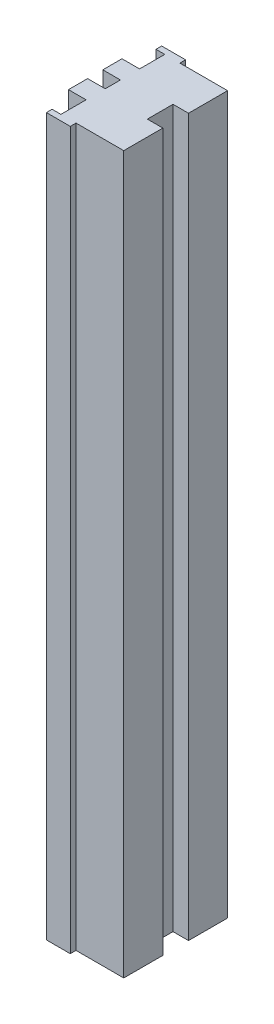
SolidWorks part; units mm, degrees
ref_plane "Спереди" through (0, 0, 0) normal (0, 0, 1) x (1, 0, 0)
ref_plane "Сверху" through (0, 0, 0) normal (0, 1, 0) x (1, 0, 0)
ref_plane "Справа" through (0, 0, 0) normal (1, 0, 0) x (0, 0, -1)
sketch "Эскиз1" plane through (0, 0, 0) normal (0, 1, 0) x (1, 0, 0)
  line L4 (-13.591, -14.9124) -> (-13.591, -7.6788)
  line L5 (-13.591, -7.6788) -> (-18.6478, -7.6788)
  line L6 (-18.6478, -7.6788) -> (-18.6478, -2.1842)
  line L7 (-18.9883, 0) -> (46.2952, 0) construction
  line L8 (-18.6478, -2.1842) -> (-13.591, -2.1842)
  line L13 (4.4514, -14.9124) -> (4.4514, -3.6855)
  line L14 (4.4514, -3.6855) -> (0, -3.6855)
  line L15 (0, -3.6855) -> (0, 3.6855)
  line L16 (-13.591, -2.1842) -> (-13.591, 2.1842)
  line L17 (-13.591, -14.9124) -> (-16.1194, -14.9124)
  line L18 (-16.1194, -14.9124) -> (-16.1194, -16.5497)
  line L19 (-16.1194, -16.5497) -> (-9.2579, -16.5497)
  line L20 (-9.2579, -16.5497) -> (-9.2579, -14.9124)
  line L21 (-9.2579, -14.9124) -> (4.4514, -14.9124)
  line L22 (-9.2579, 14.9124) -> (4.4514, 14.9124)
  line L23 (-9.2579, 16.5497) -> (-9.2579, 14.9124)
  line L24 (-16.1194, 16.5497) -> (-9.2579, 16.5497)
  line L25 (-16.1194, 14.9124) -> (-16.1194, 16.5497)
  line L26 (-13.591, 14.9124) -> (-16.1194, 14.9124)
  line L27 (4.4514, 3.6855) -> (0, 3.6855)
  line L28 (4.4514, 14.9124) -> (4.4514, 3.6855)
  line L29 (-18.6478, 2.1842) -> (-13.591, 2.1842)
  line L30 (-18.6478, 7.6788) -> (-18.6478, 2.1842)
  line L31 (-13.591, 7.6788) -> (-18.6478, 7.6788)
  line L32 (-13.591, 14.9124) -> (-13.591, 7.6788)
  point P21 (0, 0)
  point P25 (-13.591, 0)
  point P26 (0, 0)
extrude "Бобышка-Вытянуть1" add sketch "Эскиз1" along normal blind 205.74
